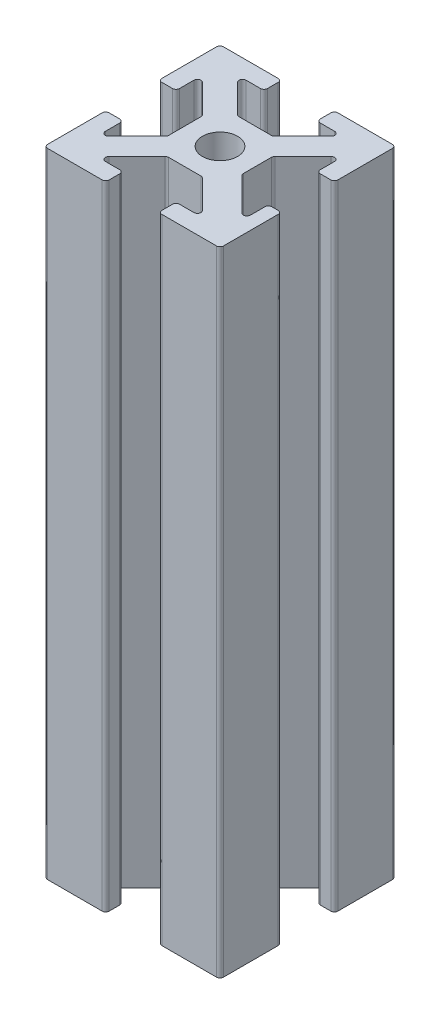
SolidWorks part; units mm, degrees
ref_plane "Plan de face" through (0, 0, 0) normal (0, 0, 1) x (1, 0, 0)
ref_plane "Plan de dessus" through (0, 0, 0) normal (0, 1, 0) x (1, 0, 0)
ref_plane "Plan de droite" through (0, 0, 0) normal (1, 0, 0) x (0, 0, -1)
sketch "Esquisse1" plane through (0, 0, 0) normal (0, 1, 0) x (1, 0, 0)
  line L0 (0, 0) -> (20, 0) construction
  line L1 (20, 0) -> (20, 20) construction
  line L2 (20, 20) -> (0, 20) construction
  line L3 (0, 20) -> (0, 0) construction
  line L4 (0, 0) -> (20, 20) construction
  line L5 (20, 20) -> (0, 20) construction
  line L6 (0, 20) -> (20, 0) construction
  line L7 (0, 0) -> (0, 7)
  line L8 (0, 20) -> (0, 13)
  line L9 (0, 20) -> (7, 20)
  line L10 (20, 20) -> (20, 13)
  line L11 (20, 20) -> (13, 20)
  line L12 (20, 0) -> (20, 7)
  line L13 (20, 0) -> (13, 0)
  line L14 (0, 0) -> (7, 0)
  line L15 (0, 7) -> (2, 7)
  line L16 (0, 13) -> (2, 13)
  line L17 (2, 13) -> (2, 16)
  line L18 (7, 0) -> (7, 2)
  line L19 (13, 0) -> (13, 2)
  line L20 (13, 2) -> (16, 2)
  line L21 (20, 7) -> (18.5, 7)
  line L22 (18.5, 7) -> (18.5, 4)
  line L23 (20, 13) -> (18, 13)
  line L24 (18, 13) -> (18, 16)
  line L25 (13, 20) -> (13, 18)
  line L26 (13, 18) -> (16, 18)
  line L27 (7, 20) -> (7, 18)
  line L28 (7, 18) -> (4, 18)
  line L29 (10, 10) -> (10, 14) construction
  line L30 (10, 14) -> (14, 14) construction
  line L31 (14, 14) -> (14, 6) construction
  line L32 (14, 6) -> (6, 6) construction
  line L33 (6, 6) -> (6, 14) construction
  line L34 (6, 14) -> (10, 14) construction
  line L42 (7, 2) -> (4, 2)
  line L44 (2, 7) -> (2, 4)
  line L49 (2, 4) -> (6, 8)
  line L50 (4, 2) -> (8, 6)
  line L51 (8, 6) -> (12, 6)
  line L52 (12, 6) -> (16, 2)
  line L53 (2, 16) -> (6, 12)
  line L54 (6, 12) -> (6, 8)
  line L55 (18.5, 4) -> (14, 8.5)
  line L56 (14, 8.5) -> (14, 12)
  line L57 (14, 12) -> (18, 16)
  line L58 (16, 18) -> (12, 14)
  line L59 (12, 14) -> (8, 14)
  line L60 (8, 14) -> (4, 18)
  circle A0 centre (10, 10) radius 2
extrude "Boss.-Extru.1" add sketch "Esquisse1" along normal blind 72
fillet "Congé1" radius 0.4 36 edges at (4, 36, -18) (2, 36, -16) (6, 36, -12) (6, 36, -8) (2, 36, -4) (2, 36, -7) (0, 36, -7) (0, 36, 0) (7, 36, 0) (7, 36, -2) (4, 36, -2) (8, 36, -6) (12, 36, -6) (16, 36, -2) (13, 36, -2) (13, 36, 0) (20, 36, 0) (20, 36, -7) (18.5, 36, -7) (18.5, 36, -4) (14, 36, -8.5) (14, 36, -12) (18, 36, -16) (18, 36, -13) (20, 36, -13) (20, 36, -20) (13, 36, -20) (13, 36, -18) (16, 36, -18) (12, 36, -14) (8, 36, -14) (7, 36, -18) (7, 36, -20) (0, 36, -20) (0, 36, -13) (2, 36, -13) first distance on face at (6, 36, -16) first distance on face at (2, 36, -14.5) first distance on face at (4, 36, -14) first distance on face at (6, 36, -10) first distance on face at (4, 36, -6) first distance on face at (2, 36, -5.5) first distance on face at (1, 36, -7) first distance on face at (0, 36, -3.5) first distance on face at (3.5, 36, 0) first distance on face at (7, 36, -1) first distance on face at (5.5, 36, -2) first distance on face at (6, 36, -4) first distance on face at (10, 36, -6) first distance on face at (14, 36, -4) first distance on face at (14.5, 36, -2) first distance on face at (13, 36, -1) first distance on face at (16.5, 36, 0) first distance on face at (20, 36, -3.5) first distance on face at (19.25, 36, -7) first distance on face at (18.5, 36, -5.5) first distance on face at (16.25, 36, -6.25) first distance on face at (14, 36, -10.25) first distance on face at (16, 36, -14) first distance on face at (18, 36, -14.5) first distance on face at (19, 36, -13) first distance on face at (20, 36, -16.5) first distance on face at (16.5, 36, -20) first distance on face at (13, 36, -19) first distance on face at (14.5, 36, -18) first distance on face at (14, 36, -16) first distance on face at (10, 36, -14) first distance on face at (5.5, 36, -18) first distance on face at (7, 36, -19) first distance on face at (3.5, 36, -20) first distance on face at (0, 36, -16.5) first distance on face at (1, 36, -13)
